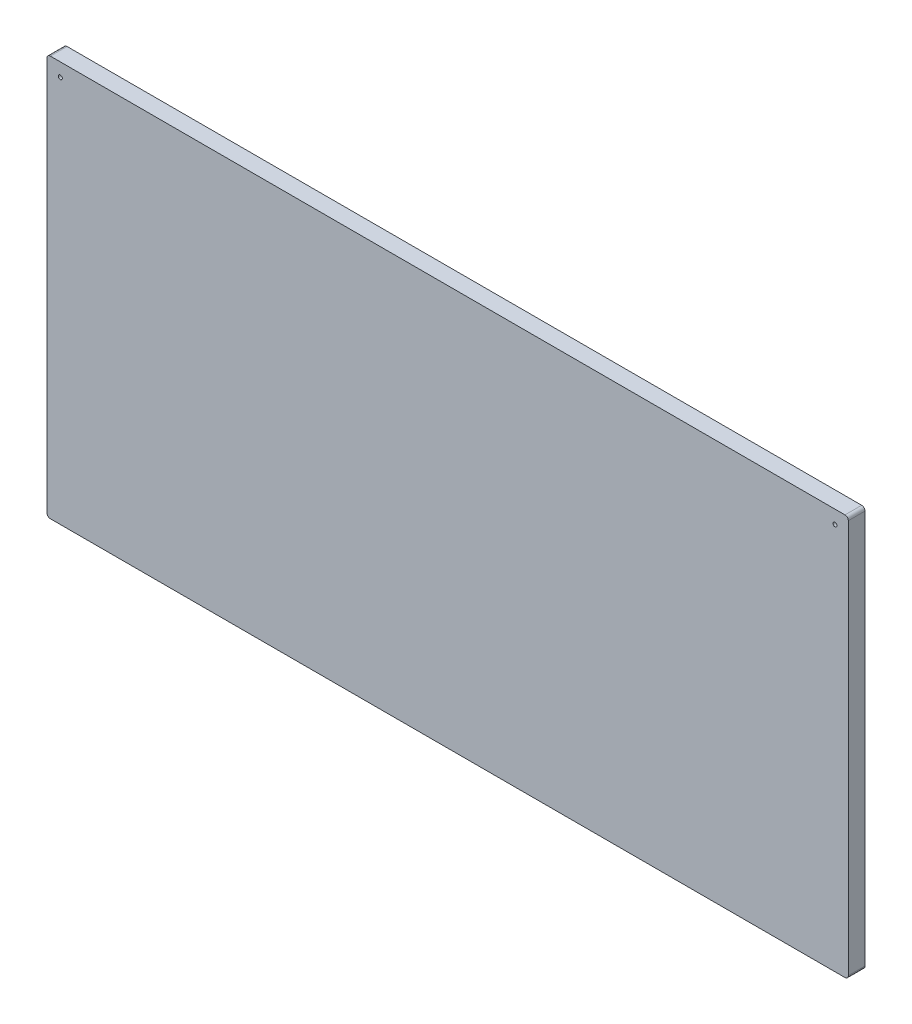
SolidWorks part; units mm, degrees
ref_plane "前视基准面" through (0, 0, 0) normal (0, 0, 1) x (1, 0, 0)
ref_plane "上视基准面" through (0, 0, 0) normal (0, 1, 0) x (1, 0, 0)
ref_plane "右视基准面" through (0, 0, 0) normal (1, 0, 0) x (0, 0, -1)
other "Configuration Table"
sketch "Sketch1" plane through (0, 0, 0) normal (0, 0, 1) x (1, 0, 0)
  line L1 (-595, -300) -> (595, -300)
  line L2 (-600, -295) -> (-600, 295)
  line L3 (-595, 300) -> (595, 300)
  line L4 (600, -295) -> (600, 295)
  line L5 (-600, -300) -> (600, 300) construction
  line L6 (-600, 300) -> (600, -300) construction
  arc A0 (595, 300) -> (600, 295) centre (595, 295) cw
  arc A1 (595, -300) -> (600, -295) centre (595, -295) ccw
  arc A2 (-600, 295) -> (-595, 300) centre (-595, 295) cw
  arc A3 (-595, -300) -> (-600, -295) centre (-595, -295) cw
  point P0 (0, 0)
  dimension "D1" = 5
  dimension "D2" = 5
  dimension "D3" = 5
  dimension "D4" = 5
extrude "Boss-Extrude1" add sketch "Sketch1" against normal blind 25
sketch "Sketch2" plane through (0, 0, 0) normal (0, 0, 1) x (1, 0, 0)
  circle A0 centre (580, 280) radius 3
  circle A1 centre (-580, 280) radius 3
extrude "Cut-Extrude1" cut sketch "Sketch2" against normal blind 27.5
ref_plane "bottom_face" through (0, 0, -25) normal (0, 0, 1) x (1, 0, 0)
ref_plane "top_face" through (0, 0, 0) normal (0, 0, 1) x (1, 0, 0)
sketch3d "3DSketch1"
  line L0 (580, 280, 0) -> (580, 280, -25) construction
ref_axis "mount_hole_axis_fl_xp_yp" through (580, 280, 0) along (0, 0, -1)
sketch3d "3DSketch2"
  line L0 (580, -280, 0) -> (580, -280, -25) construction
ref_axis "mount_hole_axis_fl_xp_ym" through (580, -280, 0) along (0, 0, -1)
sketch3d "3DSketch3"
  line L0 (-580, 280, 0) -> (-580, 280, -25) construction
ref_axis "mount_hole_axis_bl_xm_yp" through (-580, 280, 0) along (0, 0, -1)
sketch3d "3DSketch4"
  line L0 (-580, -280, 0) -> (-580, -280, -25) construction
ref_axis "mount_hole_axis_bl_xm_ym" through (-580, -280, 0) along (0, 0, -1)
